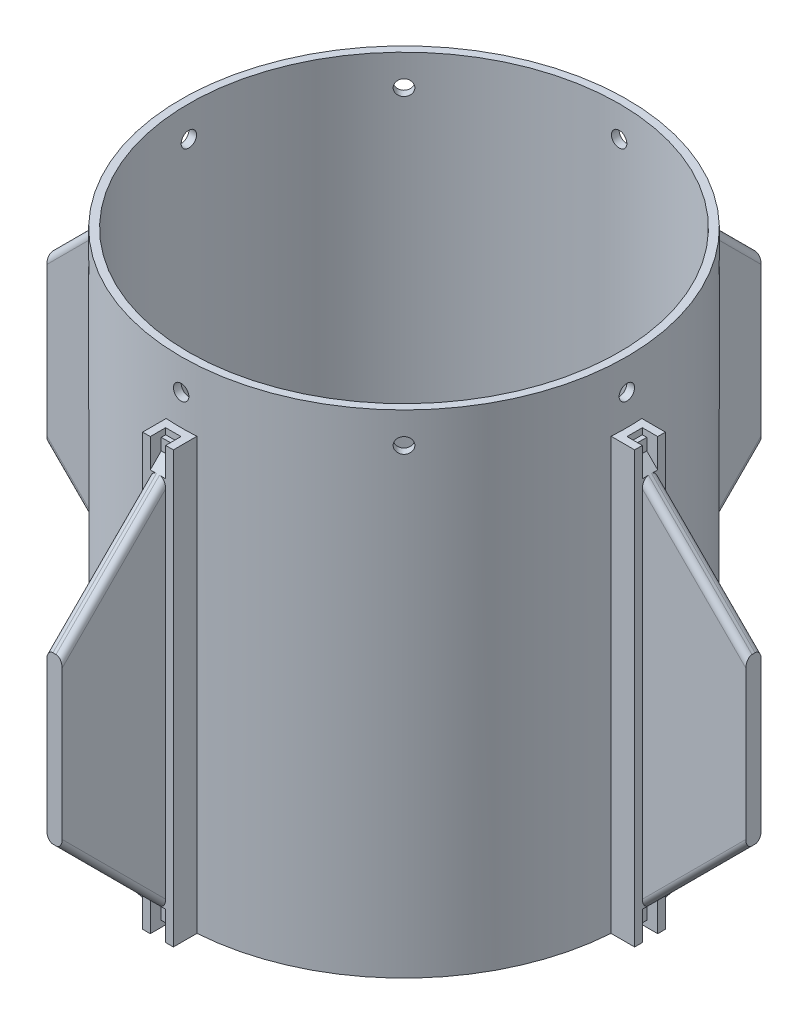
SolidWorks part; units mm, degrees
ref_plane "Front Plane" through (0, 0, 0) normal (0, 0, 1) x (1, 0, 0)
ref_plane "Top Plane" through (0, 0, 0) normal (0, 1, 0) x (1, 0, 0)
ref_plane "Right Plane" through (0, 0, 0) normal (1, 0, 0) x (0, 0, -1)
sketch "Sketch1" plane through (0, 0, 0) normal (0, 1, 0) x (1, 0, 0)
  circle A0 centre (0, 0) radius 92.075
  circle A1 centre (0, 0) radius 88.9
  dimension "D1" = 184.15
  dimension "D2" = 177.8
extrude "Base Shell" add sketch "Sketch1" along normal blind 203.2
sketch "Sketch2" plane through (0, 0, 0) normal (0, -1, 0) x (1, 0, 0)
  circle A1 centre (0, 0) radius 69.85 construction
  circle A2 centre (0, 0) radius 88.9 construction
  circle A3 centre (0, 0) radius 88.9
  arc A4 (-78.8035, -9.5078) -> (-9.5078, -78.8035) centre (0, 0) ccw
  circle A5 centre (0, 79.375) radius 3.175
  circle A6 centre (79.375, 0) radius 3.175
  circle A7 centre (0, -79.375) radius 3.175
  circle A8 centre (-79.375, 0) radius 3.175
  arc A9 (-9.5078, 78.8035) -> (9.5078, 78.8035) centre (0, 79.375) ccw
  arc A10 (78.8035, 9.5078) -> (78.8035, -9.5078) centre (79.375, 0) ccw
  arc A11 (9.5078, -78.8035) -> (-9.5078, -78.8035) centre (0, -79.375) ccw
  arc A12 (-78.8035, -9.5078) -> (-78.8035, 9.5078) centre (-79.375, 0) ccw
  arc A13 (-9.5078, 78.8035) -> (-78.8035, 9.5078) centre (0, 0) ccw
  arc A14 (78.8035, 9.5078) -> (9.5078, 78.8035) centre (0, 0) ccw
  arc A15 (9.5078, -78.8035) -> (78.8035, -9.5078) centre (0, 0) ccw
  point P18 (0, 0)
  point P26 (0, 0)
  dimension "D1" = 139.7
extrude "Bolt Insert" add sketch "Sketch2" against normal blind 6.35
sketch "Sketch3" plane through (0, 0, 0) normal (0, 1, 0) x (1, 0, 0)
  line L0 (-6.35, 0) -> (6.35, 0)
  line L7 (-6.35, 101.6) -> (-3.175, 101.6)
  line L9 (0, 101.6) -> (0, 92.075) construction
  line L10 (-6.35, 101.6) -> (-5.7435, 91.8957) construction
  line L11 (-6.35, 91.8558) -> (-6.35, 101.6)
  line L12 (5.7435, 91.8957) -> (6.35, 101.6) construction
  line L14 (6.35, 91.8558) -> (6.35, 101.6)
  line L15 (-3.175, 101.6) -> (-3.175, 95.25)
  line L16 (-3.175, 95.25) -> (3.175, 95.25)
  line L17 (3.175, 101.6) -> (3.175, 95.25)
  line L18 (0, 101.6) -> (3.175, 95.25) construction
  line L19 (-3.175, 95.25) -> (0, 101.6) construction
  line L20 (3.175, 101.6) -> (6.35, 101.6)
  circle A2 centre (0, 0) radius 92.075 construction
  arc A3 (6.35, 91.8558) -> (-6.35, 91.8558) centre (0, 0) ccw
  point P1 (0, 101.6)
  dimension "D1" = 12.7
  dimension "D2" = 101.6
  dimension "D3" = 6.35
  dimension "D4" = 3.175
  dimension "D5" = 3.175
extrude "Fin Bracket" add sketch "Sketch3" along normal blind 177.8 contours A3 L14 L20 L17 L16 L15 L7 L11 region at (-4.7625, 0, -101.4399)
pattern_circular "CirPattern1" count 4 over 360 about axis through (0, 203.2, 0) along (0, -1, 0) of "Fin Bracket"
sketch "Sketch4" plane through (0, 0, 0) normal (0, 0, 1) x (1, 0, 0)
  line L0 (0, 0) -> (95.25, 0) construction
  line L1 (91.8558, 2.54) -> (91.8558, 175.26)
  line L6 (91.8558, 177.8) -> (91.8558, 0) construction
  line L8 (91.8558, 2.54) -> (91.8558, 175.26)
  line L12 (91.8558, 175.26) -> (97.0711, 175.26)
  line L13 (97.0711, 170.3979) -> (97.0711, 175.26)
  line L14 (144.3397, 123.1293) -> (97.0711, 170.3979)
  line L15 (144.3397, 54.6707) -> (144.3397, 123.1293)
  line L16 (97.0711, 7.4021) -> (144.3397, 54.6707)
  line L17 (97.0711, 2.54) -> (97.0711, 7.4021)
  line L18 (91.8558, 2.54) -> (97.0711, 2.54)
extrude "Base Fin" add sketch "Sketch4" along normal mid plane 6.35 contours L1 region at (114.2323, 88.9, 0)
pattern_circular "Fin Pattern" count 4 over 360 about axis through (0, 203.2, 0) along (0, -1, 0) of "Base Fin"
fillet "Fin Fillets" radius 2.54 16 edges at (122.9699, 33.3009, 3.175) (122.9699, 33.3009, -3.175) (122.9699, 144.4991, -3.175) (122.9699, 144.4991, 3.175) (3.175, 33.3009, -122.9699) (-3.175, 33.3009, -122.9699) (3.175, 144.4991, -122.9699) (-3.175, 144.4991, -122.9699) (-122.9699, 144.4991, 3.175) (-122.9699, 144.4991, -3.175) (-122.9699, 33.3009, -3.175) (-122.9699, 33.3009, 3.175) (3.175, 33.3009, 122.9699) (-3.175, 33.3009, 122.9699) (3.175, 144.4991, 122.9699) (-3.175, 144.4991, 122.9699)
sketch "Sketch5" plane through (0, 0, 0) normal (0, 0, 1) x (1, 0, 0)
  line L0 (0, 203.2) -> (0, 177.8) construction
  line L1 (92.075, 203.2) -> (-92.075, 203.2) construction
  line L2 (6.35, 177.8) -> (-6.35, 177.8) construction
  circle A0 centre (0, 190.5) radius 3.175
  dimension "D1" = 6.35
extrude "Cut-Extrude1" cut sketch "Sketch5" against normal through all
pattern_circular "CirPattern2" count 8 over 360 about axis through (0, 203.2, 0) along (0, 1, 0) of "Cut-Extrude1"
